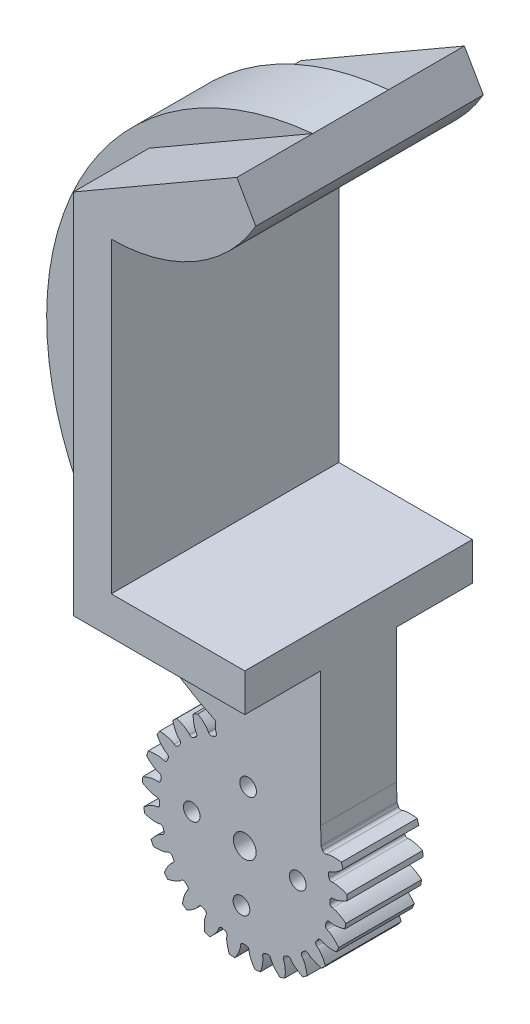
SolidWorks part; units mm, degrees
ref_plane "前视基准面" through (0, 0, 0) normal (0, 0, 1) x (1, 0, 0)
ref_plane "上视基准面" through (0, 0, 0) normal (0, 1, 0) x (1, 0, 0)
ref_plane "右视基准面" through (0, 0, 0) normal (1, 0, 0) x (0, 0, -1)
ref_axis "Axis1" through (0, 0, -88.99) along (0, 0, 1)
sketch "草图1" plane through (0, 0, 0) normal (0, 0, 1) x (1, 0, 0)
  circle A0 centre (0, 0) radius 13.5
extrude "LaShenA" add sketch "草图1" along normal blind 10
sketch "SketchA" plane through (0, 0, 10) normal (0, 0, 1) x (1, 0, 0)
  line L0 (0, 0) -> (-4.9697, 12.552) construction
  arc A0 (-3.9844, 10.5208) -> (-4.2975, 10.3968) centre (0, 0) ccw
  arc A1 (-3.4867, 13.7076) -> (-6.8418, 12.3792) centre (0, 0) ccw
  arc A2 (-4.2975, 10.3968) -> (-4.7863, 10.5857) centre (-4.4427, 10.748) cw
  arc A3 (-3.7574, 10.9931) -> (-3.9844, 10.5208) centre (-4.1189, 10.8762) cw
  circle A4 centre (0, 0) radius 11.7462 construction
  circle A5 centre (0, 0) radius 13.5 construction
  circle A6 centre (0, 0) radius 11.25 construction
  circle A7 centre (0, 0) radius 12.5 construction
  spline S0 degree 3 poles (-3.7574, 10.9931) (-3.7706, 11.0341) (-3.7936, 11.1057) (-3.8159, 11.1929) (-3.8275, 11.2557) (-3.8357, 11.3059) (-3.8435, 11.364) (-3.8507, 11.43) (-3.8569, 11.5041) (-3.8616, 11.586) (-3.8645, 11.6759) (-3.8651, 11.7737) (-3.863, 11.8792) (-3.8578, 11.9925) (-3.8492, 12.1134) (-3.8367, 12.2418) (-3.8199, 12.3776) (-3.7985, 12.5206) (-3.7721, 12.6708) (-3.7402, 12.8279) (-3.7025, 12.9917) (-3.6587, 13.1621) (-3.5901, 13.4028) (-3.5304, 13.5848) (-3.4867, 13.7076) knots 0.117691 0.117691 0.117691 0.117691 0.158672 0.189773 0.203463 0.219643 0.238312 0.25947 0.283117 0.309254 0.337879 0.368994 0.402598 0.438691 0.477273 0.518344 0.561905 0.607955 0.656494 0.707522 0.761039 0.817046 0.875541 1 1 1 1
  spline S1 degree 3 poles (-4.7863, 10.5857) (-4.8047, 10.6247) (-4.8369, 10.6927) (-4.8804, 10.7714) (-4.9149, 10.8252) (-4.9433, 10.8673) (-4.9774, 10.915) (-5.0173, 10.9682) (-5.0635, 11.0264) (-5.1162, 11.0893) (-5.1756, 11.1568) (-5.2421, 11.2285) (-5.3159, 11.304) (-5.3972, 11.383) (-5.4862, 11.4652) (-5.5832, 11.5503) (-5.6884, 11.6378) (-5.802, 11.7274) (-5.924, 11.8188) (-6.0548, 11.9115) (-6.1944, 12.0051) (-6.343, 12.0993) (-6.5577, 12.2278) (-6.7259, 12.3196) (-6.8418, 12.3792) knots 0.117691 0.117691 0.117691 0.117691 0.158672 0.189773 0.203463 0.219643 0.238312 0.25947 0.283117 0.309254 0.337879 0.368994 0.402598 0.438691 0.477273 0.518344 0.561905 0.607955 0.656494 0.707522 0.761039 0.817046 0.875541 1 1 1 1
  dimension "D1" = 0.38
  dimension "Db" = 23.4923
  dimension "Da" = 27
  dimension "Df" = 22.5
  dimension "Dn" = 25
extrude "Cut-ExtrudeA" cut sketch "SketchA" against normal blind 30
pattern_circular "www.KYTool.cn" count 25 over 360 about axis through (0, 0, -88.99) along (0, 0, 1) of "Cut-ExtrudeA"
sketch "草图4" plane through (-1.0086, -38.3291, 10) normal (0, 0, 1) x (1, 0, 0)
  line L0 (1.0086, 38.3291) -> (11.0086, 38.3291) construction
  line L1 (11.0086, 38.3291) -> (11.0086, 68.3291)
  line L2 (6.0086, 46.9893) -> (6.0086, 63.3291)
  line L3 (11.0086, 68.3291) -> (-6.5914, 68.3291)
  line L4 (-6.5914, 68.3291) -> (-6.5914, 108.8291)
  line L5 (-6.5914, 108.8291) -> (12.4612, 119.8291) construction
  line L6 (6.0086, 63.3291) -> (-11.5914, 63.3291)
  line L7 (-11.5914, 63.3291) -> (-11.5914, 111.7158)
  line L8 (-11.5914, 111.7158) -> (9.9612, 124.1592)
  line L9 (9.9612, 124.1592) -> (12.4612, 119.8291)
  line L10 (6.0086, 38.3291) -> (6.0086, 46.9893) construction
  line L11 (6.0086, 38.3291) -> (6.0086, 63.3291) construction
  line L12 (-6.5914, 108.8291) -> (12.9989, 108.8291) construction
  arc A0 (11.0086, 38.3291) -> (6.0086, 46.9893) centre (1.0086, 38.3291) ccw
  arc A1 (6.0086, 46.9893) -> (11.0086, 38.3291) centre (1.0086, 38.3291) ccw construction
  arc A2 (-6.5914, 108.8291) -> (12.4612, 119.8291) centre (-6.5914, 130.8291) ccw
  point P13 (1.0086, 38.3291)
  dimension "D1" = 20
  dimension "D3" = 30
  dimension "D4" = 17.6
  dimension "D5" = 40.5
  dimension "D6" = 22
  dimension "D7" = 120
  dimension "D2" = 5
extrude "凸台-拉伸2" add sketch "草图4" against normal blind 20 and the other way blind 10
sketch "草图6" plane through (-1.0086, -38.3291, 20) normal (0, 0, 1) x (1, 0, 0)
  line L0 (11.0086, 38.3291) -> (11.0086, 68.3291) construction
  line L1 (6.0086, 63.3291) -> (6.0086, 46.9893) construction
  line L2 (11.0086, 38.3291) -> (11.0086, 63.3291)
  line L3 (6.0086, 63.3291) -> (6.0086, 46.9893)
  line L4 (6.0086, 63.3291) -> (11.0086, 63.3291)
  arc A0 (11.0086, 38.3291) -> (6.0086, 46.9893) centre (1.0086, 38.3291) ccw construction
  arc A1 (11.0086, 38.3291) -> (6.0086, 46.9893) centre (1.0086, 38.3291) ccw
extrude "切除-拉伸2" cut sketch "草图6" against normal blind 10 contours L2 L4 L3 A1
sketch "草图8" plane through (-1.0086, -38.3291, 10) normal (0, 0, 1) x (1, 0, 0)
  line L1 (9.9612, 124.1592) -> (-11.5914, 111.7158)
  line L10 (-11.5914, 111.7158) -> (-11.5914, 63.3291)
  line L11 (-11.5914, 63.3291) -> (6.0086, 63.3291)
  line L12 (6.0086, 63.3291) -> (6.0086, 47.813)
  arc A1 (9.9612, 124.1592) -> (6.0086, 47.813) centre (13.5086, 85.7001) ccw
  point P0 (0, 0)
  point P1 (0, 0)
  point P8 (0, 0)
extrude "凸台-拉伸3" add sketch "草图8" against normal blind 10 contours L1 A1 L12 L11 L10 | L1 L10 L11 L12 A1 region at (-13.0456, 42.4923, 10)
sketch "草图10" plane through (-1.0086, -38.3291, -10) normal (0, 0, -1) x (-1, 0, 0)
  line L0 (-6.0086, 63.3291) -> (-6.0086, 46.9893) construction
  line L1 (-11.0086, 38.3291) -> (-11.0086, 68.3291) construction
  line L2 (-6.0086, 63.3291) -> (-6.0086, 46.9893)
  line L3 (-11.0086, 38.3291) -> (-11.0086, 63.3291)
  line L4 (-6.0086, 63.3291) -> (-11.0086, 63.3291)
  arc A0 (-6.0086, 46.9893) -> (-11.0086, 38.3291) centre (-1.0086, 38.3291) ccw construction
  arc A1 (-6.0086, 46.9893) -> (-11.0086, 38.3291) centre (-1.0086, 38.3291) ccw
extrude "切除-拉伸3" cut sketch "草图10" against normal blind 10
sketch "草图12" plane through (-1.0086, -38.3291, 10) normal (0, 0, 1) x (1, 0, 0)
  line L0 (-7.0754, 38.8377) -> (-4.8797, 38.6995) construction
  line L1 (-12.4647, 39.1767) -> (-7.0754, 38.8377) construction
  line L2 (2.5057, 38.2349) -> (6.897, 37.9586) construction
  line L3 (-4.8797, 38.6995) -> (-0.4884, 38.4232) construction
  line L4 (-0.4884, 38.4232) -> (2.5057, 38.2349) construction
  line L5 (9.0926, 37.8205) -> (14.482, 37.4814) construction
  line L6 (6.897, 37.9586) -> (9.0926, 37.8205) construction
  circle A3 centre (1.0086, 38.3291) radius 1.5
  circle A6 centre (-5.9776, 38.7686) radius 1.1
  circle A7 centre (1.4482, 45.3152) radius 1.1
  circle A8 centre (7.9948, 37.8895) radius 1.1
  circle A9 centre (0.5691, 31.3429) radius 1.1
  point P5 (1.0086, 38.3291)
  point P7 (1.0086, 38.3291)
  point P20 (0, 0)
  point P21 (1.0086, 38.3291)
  dimension "D1" = 2.2
  dimension "D2" = 7
  dimension "D5" = 3
  dimension "D3" = 4
extrude "切除-拉伸4" cut sketch "草图12" against normal through all
sketch "草图13" plane through (0, 0, 10) normal (0, 0, 1) x (1, 0, 0)
  arc A0 (-1.2428, 11.1811) -> (-1.1047, 11.2242) centre (-1.2847, 11.5588) ccw construction
  arc A1 (-1.2428, 11.1811) -> (-1.5769, 11.1389) centre (0, 0) ccw construction
  arc A2 (-2.0034, 11.4435) -> (-1.5769, 11.1389) centre (-1.6302, 11.5152) ccw construction
  arc A3 (-2.0335, 11.5875) -> (-1.1047, 11.2242) centre (12.5, 47.3711) ccw construction
  arc A4 (-1.2428, 11.1811) -> (-1.1047, 11.2242) centre (-1.2847, 11.5588) ccw
  arc A5 (-1.2428, 11.1811) -> (-1.5769, 11.1389) centre (0, 0) ccw
  arc A6 (-2.0034, 11.4435) -> (-1.5769, 11.1389) centre (-1.6302, 11.5152) ccw
  arc A7 (-2.0335, 11.5875) -> (-1.1047, 11.2242) centre (12.5, 47.3711) ccw
  spline S0 degree 3 poles (-2604.9432, -1479.6725) (-27.6161, 18.6175) (21.7281, 14.914) (-23.8561, -2.664) (2990.3354, -200.1216) knots -4.158948 -4.158948 -4.158948 -4.158948 0.959019 6.198291 6.198291 6.198291 6.198291 only from (-2.0335, 11.5875) to (-2.0034, 11.4435) construction
  spline S1 degree 3 poles (-2.0335, 11.5875) (-2.0321, 11.5815) (-2.0208, 11.5338) (-2.0115, 11.4858) (-2.0034, 11.4435) knots 0.953132 0.953132 0.953132 0.953132 0.959019 1 1 1 1
extrude "凸台-拉伸4" add sketch "草图13" against normal blind 10
sketch "草图14" plane through (0, 0, 10) normal (0, 0, 1) x (1, 0, 0)
  line L0 (10, 7.3128) -> (10.068, 5.0971)
  arc A0 (10.2643, 5.4415) -> (10.1065, 4.9419) centre (10.4478, 5.1088) ccw construction
  arc A1 (11.5869, 6.9277) -> (11.2019, 7.5345) centre (0, 0) ccw construction
  arc A2 (10.2643, 5.4415) -> (10.068, 5.0971) centre (10.4478, 5.1088) ccw
  arc A3 (11.5869, 6.9277) -> (11.2019, 7.5345) centre (0, 0) ccw
  arc A4 (10.068, 5.0971) -> (10.1065, 4.9419) centre (10.4478, 5.1088) ccw construction
  spline S0 degree 3 poles (1418.4519, -2642.5761) (-89.1557, 125.6299) (24.639, 28.0273) (11.4235, 6.6545) (11.34, 6.5269) (11.2576, 6.4079) (11.1769, 6.2975) (11.0981, 6.1953) (11.0216, 6.1013) (10.9479, 6.0152) (10.8771, 5.9368) (10.8098, 5.8659) (10.7462, 5.8024) (10.6867, 5.7459) (10.6315, 5.6961) (10.581, 5.6529) (10.5355, 5.6159) (10.4952, 5.5849) (10.4437, 5.5471) (5.7694, 2.5688) (-9.9049, 21.8645) (733.6909, -2905.6356) knots -23.488191 -23.488191 -23.488191 -23.488191 0.41017 0.461198 0.509737 0.555786 0.599347 0.640418 0.679001 0.715094 0.748698 0.779812 0.808438 0.834574 0.858221 0.879379 0.898048 0.914228 0.927918 0.959019 6.198182 6.198182 6.198182 6.198182 only from (11.5869, 6.9277) to (10.2643, 5.4415) construction
  spline S1 degree 3 poles (1692.7228, -2475.5526) (5.8718, -72.3175) (-3.375, 3.2577) (10.1041, 7.3448) (10.2134, 7.3749) (10.331, 7.404) (10.457, 7.4318) (10.5913, 7.4579) (10.734, 7.4817) (10.885, 7.5029) (35.8505, 10.3606) (75.7125, -134.1603) (-1787.1121, 2408.5876) knots -13.012622 -13.012622 -13.012622 -13.012622 0.368994 0.402598 0.438691 0.477273 0.518344 0.561905 0.607955 0.656494 0.707522 24.605819 24.605819 24.605819 24.605819 only from (10, 7.3128) to (11.2019, 7.5345) construction
  spline S2 degree 3 poles (11.5869, 6.9277) (11.5341, 6.8347) (11.4528, 6.6993) (11.34, 6.5269) (11.2576, 6.4079) (11.1769, 6.2975) (11.0981, 6.1953) (11.0216, 6.1013) (10.9479, 6.0152) (10.8771, 5.9368) (10.8098, 5.8659) (10.7462, 5.8024) (10.6867, 5.7459) (10.6315, 5.6961) (10.581, 5.6529) (10.5355, 5.6159) (10.4952, 5.5849) (10.4437, 5.5471) (10.3678, 5.4988) (10.302, 5.4623) (10.2643, 5.4415) knots 0.358993 0.358993 0.358993 0.358993 0.461198 0.509737 0.555786 0.599347 0.640418 0.679001 0.715094 0.748698 0.779812 0.808438 0.834574 0.858221 0.879379 0.898048 0.914228 0.927918 0.959019 1 1 1 1
  spline S3 degree 3 poles (10, 7.3128) (10.0338, 7.3235) (10.1038, 7.3447) (10.2134, 7.3749) (10.331, 7.404) (10.457, 7.4318) (10.5913, 7.4579) (10.734, 7.4817) (10.9381, 7.5104) (11.0952, 7.5263) (11.2019, 7.5345) knots 0.368766 0.368766 0.368766 0.368766 0.402598 0.438691 0.477273 0.518344 0.561905 0.607955 0.656494 0.758699 0.758699 0.758699 0.758699
extrude "切除-拉伸5" cut sketch "草图14" against normal blind 10
